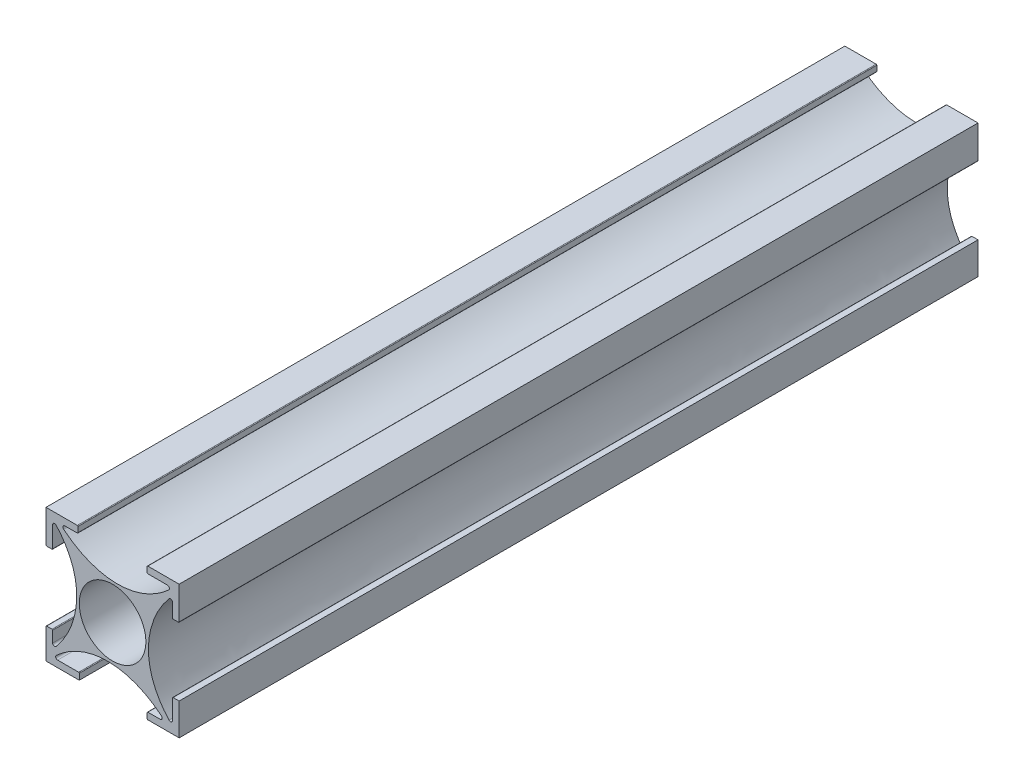
SolidWorks part; units mm, degrees
ref_plane "Front Plane" through (0, 0, 0) normal (0, 0, 1) x (1, 0, 0)
ref_plane "Top Plane" through (0, 0, 0) normal (0, 1, 0) x (1, 0, 0)
ref_plane "Right Plane" through (0, 0, 0) normal (1, 0, 0) x (0, 0, -1)
sketch "Sketch1" plane through (0, 0, 0) normal (0, 0, 1) x (1, 0, 0)
  line L1 (10, -10) -> (-10, -10)
  line L2 (10, -10) -> (10, 10)
  line L3 (10, 10) -> (-10, 10)
  line L4 (-10, -10) -> (-10, 10)
  line L5 (10, -10) -> (-10, 10) construction
  line L6 (10, 10) -> (-10, -10) construction
  point P0 (0, 0)
  dimension "D1" = 20
  dimension "D2" = 20
extrude "Boss-Extrude1" add sketch "Sketch1" along normal blind 120
sketch "Sketch2" plane through (0, 0, 0) normal (0, 0, -1) x (-1, 0, 0)
  line L2 (-9, 7.1576) -> (-9, 5.1)
  line L3 (7.1576, 9) -> (5.3, 9)
  line L4 (9, -7.1576) -> (9, -5.5)
  line L5 (-7.1576, -9) -> (-5.3, -9)
  line L6 (-5.2, 9.9) -> (-5.2, 9.1)
  line L7 (-10, 10) -> (10, 10) construction
  line L8 (-10, -10) -> (-10, 10) construction
  line L9 (9.9, 5) -> (9.1, 5)
  line L10 (-8.4691, 7.3492) -> (-4.894, 3.0412) construction
  line L11 (-4.894, 3.0412) -> (-3.8491, -3.316) construction
  line L12 (-3.8491, -3.316) -> (-8.4772, -8.4497) construction
  line L13 (7.3492, 8.4691) -> (3.0412, 4.894) construction
  line L14 (3.0412, 4.894) -> (-3.316, 3.8491) construction
  line L15 (-3.316, 3.8491) -> (-8.4497, 8.4772) construction
  line L16 (8.4691, -7.3492) -> (4.894, -3.0412) construction
  line L17 (4.894, -3.0412) -> (3.8491, 3.316) construction
  line L18 (3.8491, 3.316) -> (8.4772, 8.4497) construction
  line L19 (-7.3492, -8.4691) -> (-3.0412, -4.894) construction
  line L20 (-3.0412, -4.894) -> (3.316, -3.8491) construction
  line L21 (3.316, -3.8491) -> (8.4497, -8.4772) construction
  line L22 (-9.9, 5) -> (-9.1, 5)
  line L23 (5.2, 9.9) -> (5.2, 9.1)
  line L24 (9.9, -5.4) -> (9.1, -5.4)
  line L25 (-5.2, -9.9) -> (-5.2, -9.1)
  line L26 (5, -10) -> (5, -9.1)
  line L27 (-10, -5.2) -> (-9.1, -5.2)
  line L28 (9, 5.1) -> (9, 8.2488)
  line L29 (-5.3, 9) -> (-8.2488, 9)
  line L30 (-9, -5.3) -> (-9, -8.2488)
  line L31 (5.1, -9) -> (8.2488, -9)
  line L32 (-5.3, 10) -> (-10, 10)
  line L33 (-10, 10) -> (-10, 5.1)
  line L34 (5.3, 10) -> (10, 10)
  line L35 (10, 10) -> (10, 5.1)
  line L36 (10, -5.5) -> (10, -10)
  line L37 (10, -10) -> (5, -10)
  line L38 (-5.3, -10) -> (-10, -10)
  line L39 (-10, -10) -> (-10, -5.2)
  circle A0 centre (0, 0) radius 5
  arc A1 (8.4691, -7.3492) -> (9, -7.1576) centre (8.7, -7.1576) ccw
  arc A2 (8.2488, -9) -> (8.4497, -8.4772) centre (8.2488, -8.7) ccw
  arc A3 (-7.1576, -9) -> (-7.3492, -8.4691) centre (-7.1576, -8.7) cw
  arc A4 (-8.4772, -8.4497) -> (-9, -8.2488) centre (-8.7, -8.2488) cw
  arc A5 (-8.4691, 7.3492) -> (-9, 7.1576) centre (-8.7, 7.1576) ccw
  arc A6 (9, -5.5) -> (9.1, -5.4) centre (9.1, -5.5) cw
  arc A7 (5, -9.1) -> (5.1, -9) centre (5.1, -9.1) cw
  arc A8 (-9, -5.3) -> (-9.1, -5.2) centre (-9.1, -5.3) ccw
  arc A9 (-5.2, -9.1) -> (-5.3, -9) centre (-5.3, -9.1) ccw
  arc A10 (-5.3, 9) -> (-5.2, 9.1) centre (-5.3, 9.1) ccw
  arc A11 (-8.4497, 8.4772) -> (-8.2488, 9) centre (-8.2488, 8.7) cw
  arc A12 (5.3, 9) -> (5.2, 9.1) centre (5.3, 9.1) cw
  arc A13 (7.3492, 8.4691) -> (7.1576, 9) centre (7.1576, 8.7) ccw
  arc A14 (9, 8.2488) -> (8.4772, 8.4497) centre (8.7, 8.2488) ccw
  arc A15 (9, 5.1) -> (9.1, 5) centre (9.1, 5.1) ccw
  arc A16 (-5.2, 9.9) -> (-5.3, 10) centre (-5.3, 9.9) ccw
  arc A17 (-9.9, 5) -> (-10, 5.1) centre (-9.9, 5.1) cw
  arc A18 (-9.1, 5) -> (-9, 5.1) centre (-9.1, 5.1) ccw
  arc A19 (-5.3, -10) -> (-5.2, -9.9) centre (-5.3, -9.9) ccw
  arc A20 (9.9, 5) -> (10, 5.1) centre (9.9, 5.1) ccw
  arc A21 (5.2, 9.9) -> (5.3, 10) centre (5.3, 9.9) cw
  arc A22 (10, -5.5) -> (9.9, -5.4) centre (9.9, -5.5) ccw
  spline S0 degree 3 poles (-8.4691, 7.3492) (-4.894, 3.0412) (-3.8491, -3.316) (-8.4772, -8.4497) knots 0 0 0 0 1 1 1 1
  spline S1 degree 3 poles (7.3492, 8.4691) (3.0412, 4.894) (-3.316, 3.8491) (-8.4497, 8.4772) knots 0 0 0 0 1 1 1 1
  spline S2 degree 3 poles (8.4691, -7.3492) (4.894, -3.0412) (3.8491, 3.316) (8.4772, 8.4497) knots 0 0 0 0 1 1 1 1
  spline S3 degree 3 poles (-7.3492, -8.4691) (-3.0412, -4.894) (3.316, -3.8491) (8.4497, -8.4772) knots 0 0 0 0 1 1 1 1
  point P81 (-5.2, 10)
  point P84 (-10, 5)
  point P93 (5.2, 10)
  dimension "D1" = 4
  dimension "D5" = 4
  dimension "D4" = 0.3
  dimension "D8" = 0.3
  dimension "D9" = 0.3
  dimension "D10" = 0.3
  dimension "D11" = 0.3
  dimension "D12" = 0.1
  dimension "D13" = 0.1
  dimension "D14" = 0.1
  dimension "D15" = 0.1
  dimension "D16" = 0.1
  dimension "D17" = 0.3
  dimension "D18" = 0.1
  dimension "D19" = 0.3
  dimension "D20" = 0.3
  dimension "D21" = 0.1
  dimension "D22" = 0.1
  dimension "D23" = 0.1
  dimension "D24" = 0.1
  dimension "D25" = 0.1
  dimension "D26" = 0.1
  dimension "D27" = 0.1
  dimension "D28" = 0.1
  dimension "D2" = 1
  dimension "D3" = 4
  dimension "D6" = 5
  dimension "D7" = 4
extrude "Boss-Extrude2" add sketch "Sketch2" along normal blind 120
sketch "Sketch3" plane through (0, 0, 120) normal (0, 0, 1) x (1, 0, 0)
  line L0 (10, 10) -> (-10, 10) construction
  line L1 (10, -10) -> (-10, -10)
  line L2 (10, -10) -> (10, 10)
  line L3 (10, 10) -> (-10, 10)
  line L4 (-10, -10) -> (-10, 10)
  line L5 (10, -10) -> (-10, 10) construction
  line L6 (10, 10) -> (-10, -10) construction
  point P0 (0, 0)
extrude "Cut-Extrude1" cut sketch "Sketch3" against normal blind 120
